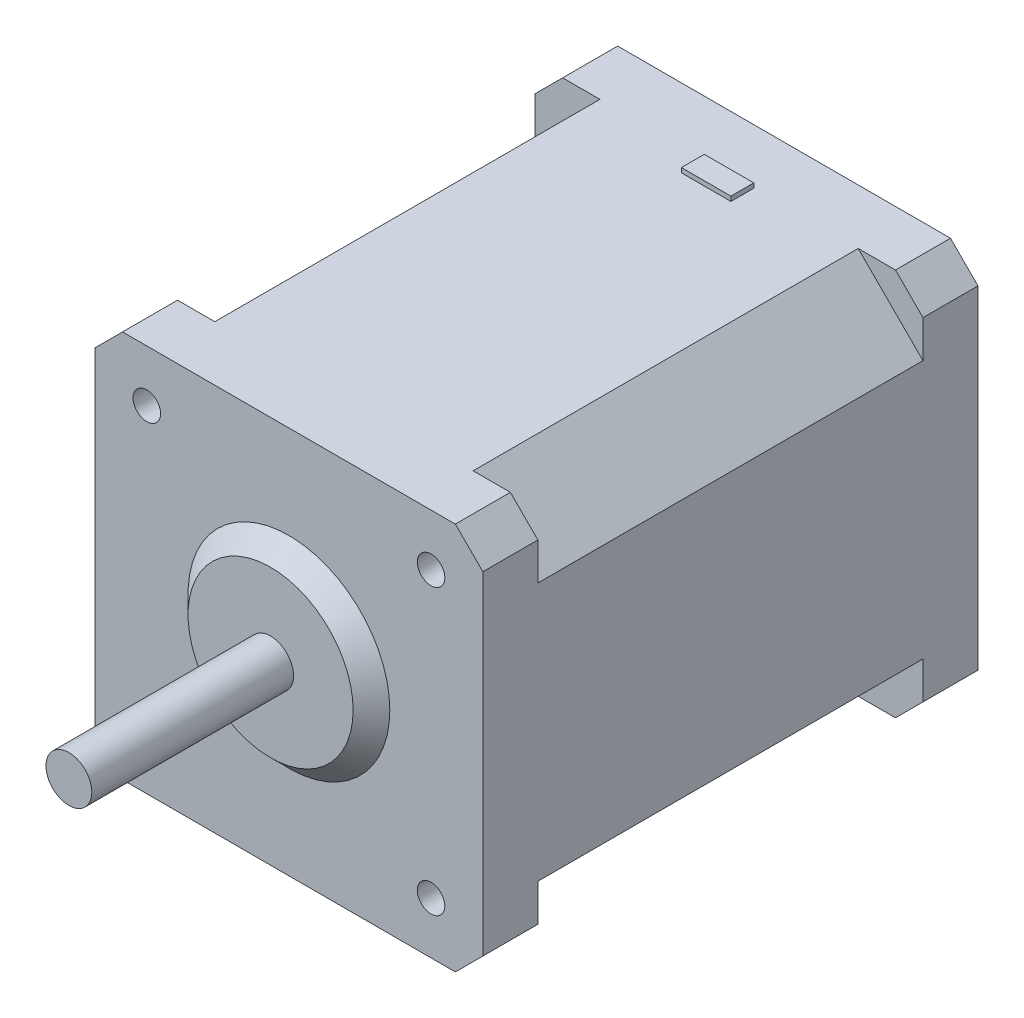
SolidWorks part; units mm, degrees
ref_plane "前视" through (0, 0, 0) normal (0, 0, 1) x (1, 0, 0)
ref_plane "上视" through (0, 0, 0) normal (0, 1, 0) x (1, 0, 0)
ref_plane "右视" through (0, 0, 0) normal (1, 0, 0) x (0, 0, -1)
sketch "草图1" plane through (0, 0, 0) normal (0, 0, 1) x (1, 0, 0)
  line L5 (19.138, 23.3719) -> (-23.162, 23.3719)
  line L6 (-23.162, 23.3719) -> (-23.162, -18.9281)
  line L7 (-23.162, -18.9281) -> (19.138, -18.9281)
  line L8 (19.138, -18.9281) -> (19.138, 23.3719)
  circle A0 centre (-17.512, 17.7219) radius 1.5
  circle A1 centre (13.488, 17.7219) radius 1.5
  circle A2 centre (-17.512, -13.2781) radius 1.5
  circle A3 centre (13.488, -13.2781) radius 1.5
  circle A6 centre (-2.012, 2.2219) radius 21.15 construction
  dimension "D1" = 31
  dimension "D2" = 31
extrude "凸台-拉伸1" add sketch "草图1" along normal blind 6
sketch "草图2" plane through (0, 0, 6) normal (0, 0, 1) x (1, 0, 0)
  line L0 (-16.8049, -18.221) -> (-22.4549, -12.571)
  line L1 (-23.162, -18.9281) -> (19.138, -18.9281) construction
  line L2 (-22.4549, 17.0148) -> (-16.8049, 22.6648)
  line L3 (-23.162, 23.3719) -> (-23.162, -18.9281) construction
  line L4 (-22.4549, -12.571) -> (-23.162, -11.8639)
  line L5 (-16.8049, -18.221) -> (-16.0978, -18.9281)
  line L6 (-16.8049, 22.6648) -> (-16.0978, 23.3719)
  line L7 (-22.4549, 17.0148) -> (-23.162, 16.3077)
  line L8 (12.7809, 22.6648) -> (18.4309, 17.0148)
  line L9 (18.4309, 17.0148) -> (19.138, 16.3077)
  line L10 (12.7809, 22.6648) -> (12.0738, 23.3719)
  line L11 (18.4309, -12.571) -> (12.7809, -18.221)
  line L12 (12.7809, -18.221) -> (12.0738, -18.9281)
  line L13 (18.4309, -12.571) -> (19.138, -11.8639)
  line L14 (-16.0978, 23.3719) -> (12.0738, 23.3719)
  line L15 (19.138, 16.3077) -> (19.138, -11.8639)
  line L16 (12.0738, -18.9281) -> (-16.0978, -18.9281)
  line L17 (-23.162, -11.8639) -> (-23.162, 16.3077)
  point P26 (-2.012, 2.2219)
  dimension "D1" = 4
extrude "凸台-拉伸2" add sketch "草图2" along normal blind 42
sketch "草图3" plane through (0, 0, 48) normal (0, 0, 1) x (1, 0, 0)
  line L1 (-23.162, 23.3719) -> (19.138, 23.3719)
  line L2 (-23.162, 23.3719) -> (-23.162, -18.9281)
  line L3 (-23.162, -18.9281) -> (19.138, -18.9281)
  line L4 (19.138, 23.3719) -> (19.138, -18.9281)
extrude "凸台-拉伸3" add sketch "草图3" along normal blind 6
sketch "草图4" plane through (0, 0, 54) normal (0, 0, 1) x (1, 0, 0)
  circle A1 centre (-2.012, 2.2219) radius 11
  circle A2 centre (-2.012, 2.2219) radius 2.5
extrude "凸台-拉伸4" add sketch "草图4" along normal blind 24 contours A2 region at (-2.012, 2.2219, 54)
extrude "凸台-拉伸5" add sketch "草图4<3>" along normal blind 2
sketch "草图4<3>" plane through (0, 0, 54) normal (0, 0, 1) x (1, 0, 0) same geometry as "草图4"
chamfer "倒角1" distance 3 angle 45 8 edges at (-23.162, -18.9281, 51) (-23.162, -18.9281, 3) (19.138, -18.9281, 51) (19.138, -18.9281, 3) (19.138, 23.3719, 51) (19.138, 23.3719, 3) (-23.162, 23.3719, 51) (-23.162, 23.3719, 3)
sketch "草图5" plane through (0, 0, 54) normal (0, 0, 1) x (1, 0, 0)
  circle A2 centre (-17.512, 17.7219) radius 1.5
  circle A3 centre (13.488, 17.7219) radius 1.5
  circle A4 centre (13.488, -13.2781) radius 1.5
  circle A5 centre (-17.512, -13.2781) radius 1.5
extrude "切除-拉伸1" cut sketch "草图5" against normal blind 6
sketch "草图6" plane through (0, 23.3719, 0) normal (0, 1, 0) x (1, 0, 0)
  line L1 (-4.7115, -6) -> (-4.7115, -8.5)
  line L2 (-4.7115, -6) -> (0.6874, -6)
  line L4 (-4.7115, -8.5) -> (0.6874, -8.5)
  line L5 (0.6874, -6) -> (0.6874, -8.5)
extrude "凸台-拉伸6" add sketch "草图6" along normal blind 0.5
chamfer "倒角2" distance 2 angle 45 1 edges at (8.988, 2.2219, 56)
